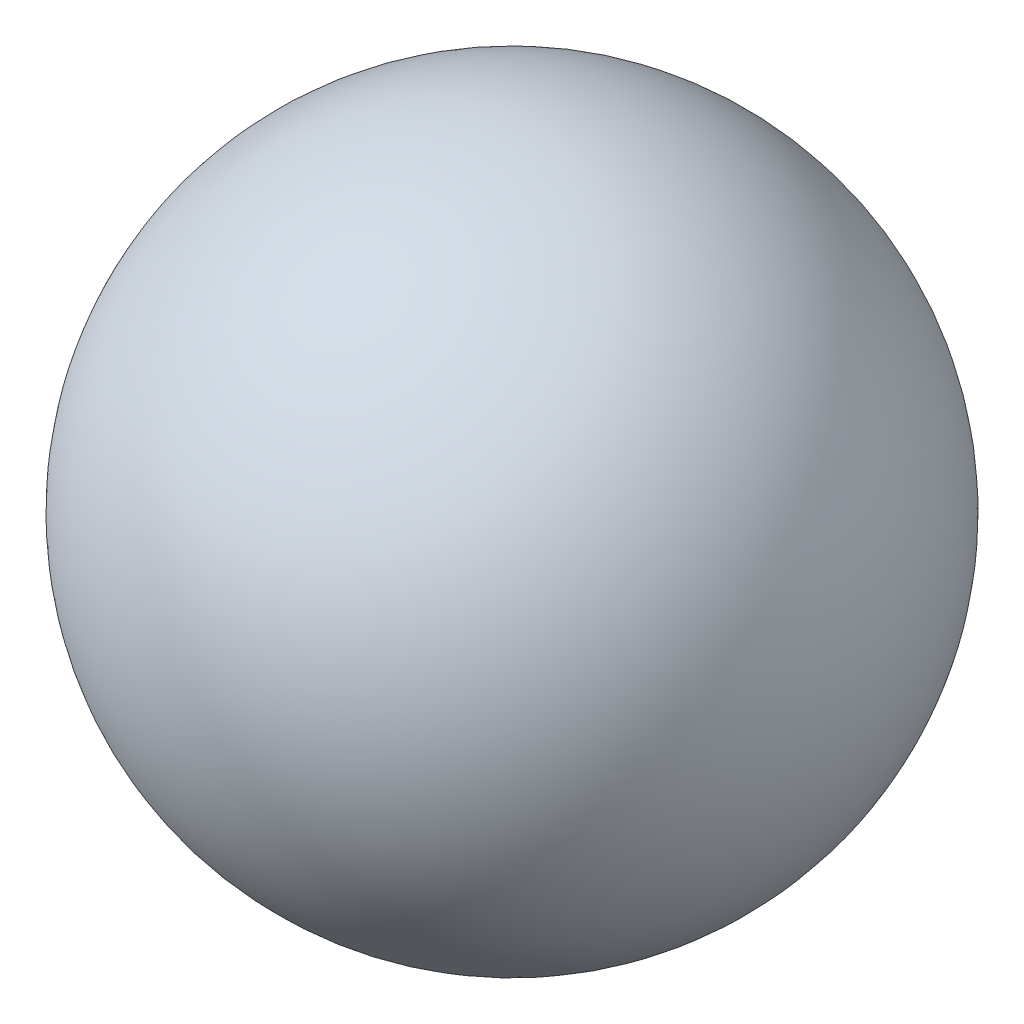
SolidWorks part; units mm, degrees
ref_plane "Front Plane" through (0, 0, 0) normal (0, 0, 1) x (1, 0, 0)
ref_plane "Top Plane" through (0, 0, 0) normal (0, 1, 0) x (1, 0, 0)
ref_plane "Right Plane" through (0, 0, 0) normal (1, 0, 0) x (0, 0, -1)
sketch "Sketch1" plane through (0, 0, 0) normal (0, 1, 0) x (1, 0, 0)
  line L0 (-27.6247, 0) -> (27.6247, 0)
  arc A0 (-27.6247, 0) -> (27.6247, 0) centre (0, 0) cw
revolve "Revolve1" add sketch "Sketch1" angle 360 about L0
